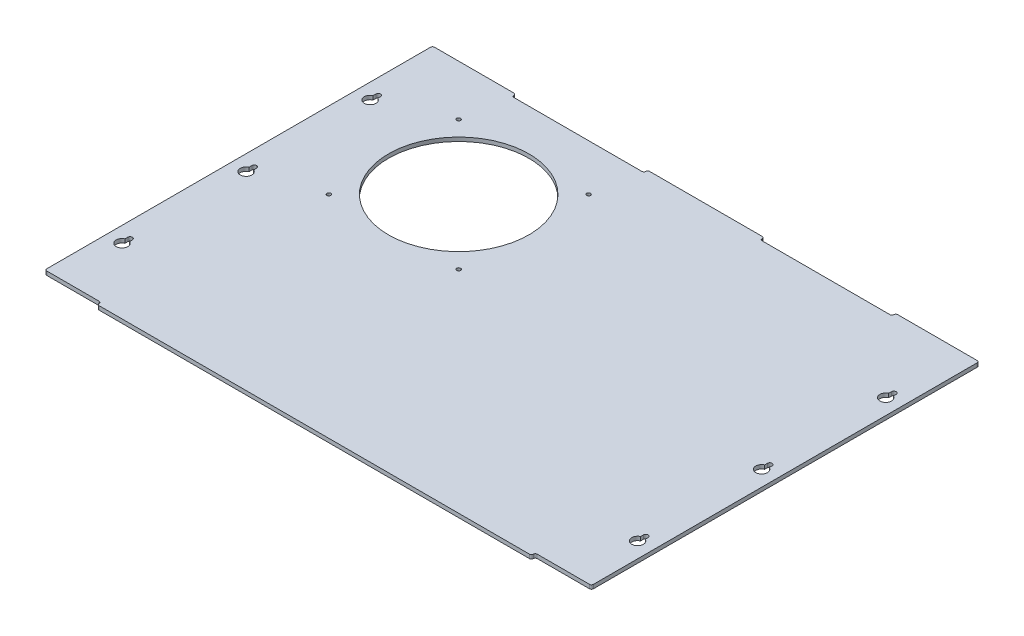
SolidWorks part; units mm, degrees
ref_plane "Front Plane" through (0, 0, 0) normal (0, 0, 1) x (1, 0, 0)
ref_plane "Top Plane" through (0, 0, 0) normal (0, 1, 0) x (1, 0, 0)
ref_plane "Right Plane" through (0, 0, 0) normal (1, 0, 0) x (0, 0, -1)
sketch "Sketch1" plane through (0, 0, 0) normal (0, 1, 0) x (1, 0, 0)
  line L0 (401.6375, 0) -> (447.675, 0)
  line L1 (0, 0) -> (46.0375, 0)
  line L2 (0, 0) -> (0, 317.5)
  line L3 (0, 317.5) -> (447.675, 317.5)
  line L4 (447.675, 0) -> (447.675, 317.5)
  line L6 (46.0375, 0) -> (46.0375, -3.175)
  line L7 (46.0375, -3.175) -> (401.6375, -3.175)
  line L8 (401.6375, 0) -> (401.6375, -3.175)
  point P9 (223.8375, -3.175)
  point P10 (223.8375, 317.5)
  dimension "D1" = 447.675
  dimension "D2" = 317.5
  dimension "D3" = 355.6
  dimension "D4" = 3.175
extrude "Boss-Extrude1" add sketch "Sketch1" along normal blind 3.175
sketch "Sketch3" plane through (0, 3.175, 0) normal (0, 1, 0) x (1, 0, 0)
  line L0 (447.675, 317.5) -> (0, 317.5) construction
  line L1 (68.2625, 317.5) -> (176.2125, 317.5)
  line L2 (68.2625, 317.5) -> (68.2625, 314.325)
  line L3 (68.2625, 314.325) -> (176.2125, 314.325)
  line L4 (176.2125, 317.5) -> (176.2125, 314.325)
  line L5 (176.2125, 314.325) -> (271.4625, 314.325) construction
  line L6 (271.4625, 317.5) -> (379.4125, 317.5)
  line L7 (271.4625, 317.5) -> (271.4625, 314.325)
  line L8 (271.4625, 314.325) -> (379.4125, 314.325)
  line L9 (379.4125, 317.5) -> (379.4125, 314.325)
  point P10 (223.8375, 317.5)
  point P11 (223.8375, 314.325)
  dimension "D1" = 3.175
  dimension "D2" = 107.95
  dimension "D3" = 95.25
extrude "Cut-Extrude2" cut sketch "Sketch3" against normal through all
fillet "Fillet1" radius 1.5875 16 edges at (379.4125, 1.5875, -317.5) (271.4625, 1.5875, -317.5) (176.2125, 1.5875, -317.5) (68.2625, 1.5875, -317.5) (379.4125, 1.5875, -314.325) (271.4625, 1.5875, -314.325) (176.2125, 1.5875, -314.325) (68.2625, 1.5875, -314.325) (447.675, 1.5875, -317.5) (447.675, 1.5875, 0) (0, 1.5875, 0) (0, 1.5875, -317.5) (401.6375, 1.5875, 3.175) (401.6375, 1.5875, 0) (46.0375, 1.5875, 3.175) (46.0375, 1.5875, 0)
sketch "Sketch2" plane through (0, 3.175, 0) normal (0, 1, 0) x (1, 0, 0)
  line L0 (0, 315.9125) -> (0, 1.5875) construction
  line L3 (66.675, 317.5) -> (1.5875, 317.5) construction
  line L7 (12.7, 253.6825) -> (12.7, 260.35) construction
  line L8 (10.795, 258.0474) -> (10.795, 260.35)
  line L9 (14.605, 258.0474) -> (14.605, 260.35)
  arc A3 (10.795, 258.0474) -> (14.605, 258.0474) centre (12.7, 253.6825) ccw
  arc A4 (14.605, 260.35) -> (10.795, 260.35) centre (12.7, 260.35) ccw
  point P17 (14.6321, 297.909)
  dimension "D2" = 57.15
  dimension "D6" = 9.525
  dimension "D1" = 12.7
  dimension "D5" = 3.81
  dimension "D7" = 6.6675
extrude "Cut-Extrude1" cut sketch "Sketch2" against normal through all
pattern_linear "LPattern1" count 3 spacing 101.6 along (0, 0, 1) of "Cut-Extrude1"
ref_plane "Plane1" through (223.8375, 0, 0) normal (-1, 0, 0) x (0, 0, 1)
mirror "Mirror1" about plane through (223.8375, 0, 0) normal (-1, 0, 0) of "LPattern1"
sketch "Sketch4" plane through (0, 3.175, 0) normal (0, 1, 0) x (1, 0, 0)
  line L0 (223.8375, 1.7463) -> (223.8375, -1.7463) construction
  line L1 (55.8875, 283.0438) -> (175.8875, 283.0438) construction
  line L2 (55.8875, 283.0438) -> (55.8875, 163.0437) construction
  line L3 (55.8875, 163.0437) -> (175.8875, 163.0437) construction
  line L4 (175.8875, 283.0438) -> (175.8875, 163.0437) construction
  line L6 (62.7063, 276.225) -> (169.0687, 276.225) construction
  line L7 (69.85, 314.325) -> (174.625, 314.325) construction
  line L8 (62.7063, 276.225) -> (62.7063, 169.8625) construction
  line L9 (62.7063, 169.8625) -> (169.0687, 169.8625) construction
  line L10 (169.0687, 276.225) -> (169.0687, 169.8625) construction
  circle A0 centre (62.7063, 276.225) radius 1.5875
  circle A1 centre (169.0687, 276.225) radius 1.5875
  circle A2 centre (169.0687, 169.8625) radius 1.5875
  circle A3 centre (62.7063, 169.8625) radius 1.5875
  circle A4 centre (115.8875, 223.0438) radius 57.5
  point P13 (115.8875, 283.0438)
  point P21 (115.8875, 276.225)
  point P26 (175.8875, 223.0438)
  point P33 (169.0687, 223.0438)
  dimension "D3" = 3.175
  dimension "D9" = 115
  dimension "D1" = 120
  dimension "D2" = 120
  dimension "D4" = 106.3625
  dimension "D8" = 38.1
  dimension "D10" = 107.95
extrude "Cut-Extrude3" cut sketch "Sketch4" against normal through all
